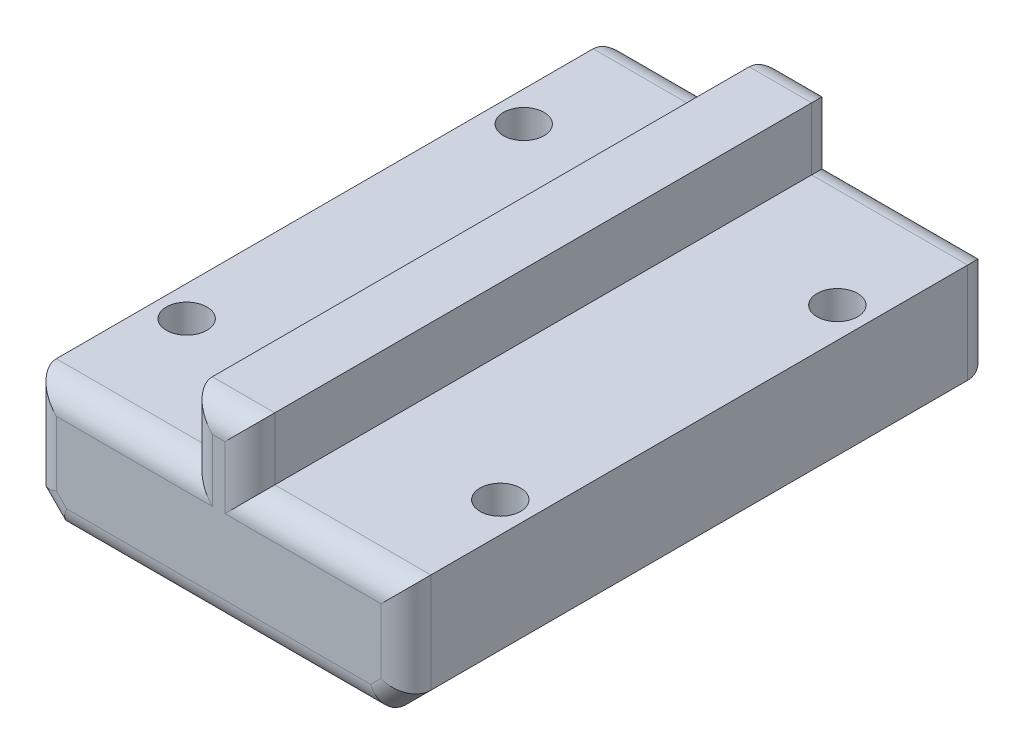
SolidWorks part; units mm, degrees
ref_plane "Front Plane" through (0, 0, 0) normal (0, 0, 1) x (1, 0, 0)
ref_plane "Top Plane" through (0, 0, 0) normal (0, 1, 0) x (1, 0, 0)
ref_plane "Right Plane" through (0, 0, 0) normal (1, 0, 0) x (0, 0, -1)
sketch "Sketch1" plane through (0, 0, 0) normal (0, 1, 0) x (1, 0, 0)
  line L1 (-15, -23.5) -> (15, -23.5)
  line L2 (-15, -23.5) -> (-15, 23.5)
  line L3 (-15, 23.5) -> (15, 23.5)
  line L4 (15, -23.5) -> (15, 23.5)
  line L5 (-15, -23.5) -> (15, 23.5) construction
  line L6 (-15, 23.5) -> (15, -23.5) construction
  point P0 (0, 0)
  dimension "D1" = 30
  dimension "D2" = 47
extrude "Boss-Extrude1" add sketch "Sketch1" along normal blind 10
sketch "Sketch2" plane through (0, 10, 0) normal (0, 1, 0) x (1, 0, 0)
  line L0 (15, 23.5) -> (-15, 23.5) construction
  line L1 (-2.5, -23.5) -> (2.5, -23.5)
  line L2 (-2.5, -23.5) -> (-2.5, 23.5)
  line L3 (-2.5, 23.5) -> (2.5, 23.5)
  line L4 (2.5, -23.5) -> (2.5, 23.5)
  line L5 (-2.5, -23.5) -> (2.5, 23.5) construction
  line L6 (-2.5, 23.5) -> (2.5, -23.5) construction
  point P0 (0, 0)
  dimension "D1" = 5
extrude "Boss-Extrude2" add sketch "Sketch2" along normal blind 5
sketch "Sketch3" plane through (0, 0, 0) normal (0, -1, 0) x (1, 0, 0)
  line L0 (-12.56, -23.5) -> (-12.56, -13.5) construction
  line L1 (15, -23.5) -> (-15, -23.5) construction
  line L2 (12.56, -23.5) -> (12.56, -13.5) construction
  line L3 (12.56, 23.5) -> (12.56, 13.5) construction
  line L4 (-15, 23.5) -> (15, 23.5) construction
  line L5 (-12.56, 23.5) -> (-12.56, 13.5) construction
  line L6 (-15, -23.5) -> (-15, 23.5) construction
  line L7 (15, 23.5) -> (15, -23.5) construction
  circle A0 centre (-12.56, 13.5) radius 1.625
  circle A1 centre (-12.56, -13.5) radius 1.625
  circle A2 centre (12.56, -13.5) radius 1.625
  circle A3 centre (12.56, 13.5) radius 1.625
  dimension "D7" = 3.25
  dimension "D8" = 3.25
  dimension "D9" = 3.25
  dimension "D10" = 3.25
  dimension "D1" = 10
  dimension "D2" = 2.44
  dimension "D3" = 2.44
  dimension "D4" = 10
  dimension "D5" = 10
  dimension "D6" = 10
extrude "Cut-Extrude1" cut sketch "Sketch3" against normal through all
sketch "Sketch4" plane through (0, 0, 0) normal (0, -1, 0) x (1, 0, 0)
  circle A0 centre (-12.56, 13.5) radius 2.7
  circle A1 centre (-12.56, -13.5) radius 2.7
  circle A2 centre (12.56, -13.5) radius 2.7
  circle A3 centre (12.56, 13.5) radius 2.7
  dimension "D1" = 5.4
  dimension "D2" = 5.4
  dimension "D3" = 5.4
  dimension "D4" = 5.4
extrude "Cut-Extrude2" cut sketch "Sketch4" against normal blind 1.45
chamfer "Chamfer1" distance 2 angle 45 1 edges at (-15, 0, 0)
chamfer "Chamfer2" distance 2 angle 45 1 edges at (15, 0, 0)
fillet "Fillet1" radius 2 10 edges at (-14, 1, 23.5) (-15, 6, 23.5) (0, 15, 23.5) (15, 6, 23.5) (14, 1, 23.5) (0, 0, 23.5)
fillet "Fillet2" radius 2 10 edges at (0, 15, -23.5) (-15, 6, -23.5) (-14, 1, -23.5) (0, 0, -23.5) (14, 1, -23.5) (15, 6, -23.5)
sketch "Mobious Logo" plane through (0, 0, 0) normal (0, -1, 0) x (1, 0, 0)
  line L0 (-8.9286, -5.3935) -> (-8.9286, -6.9382)
  line L1 (-8.9286, -6.9382) -> (0.654, -12.5149)
  line L2 (0.654, -12.5149) -> (0.654, -3.4298)
  line L3 (0.654, -3.4298) -> (-0.9494, -4.2487)
  line L4 (-0.9494, -4.2487) -> (-0.9494, -10.1586)
  line L5 (-0.9494, -10.1586) -> (-8.9286, -5.3935)
  line L6 (-4.0849, -5.6815) -> (-5.2369, -4.9745)
  line L7 (-5.2369, -4.9745) -> (2.6438, -0.4713)
  line L8 (2.6438, -0.4713) -> (2.6438, -12.1746)
  line L9 (2.6438, -12.1746) -> (1.0991, -12.5208)
  line L10 (1.0991, -12.5208) -> (1.0991, -2.5554)
  line L11 (1.0991, -2.5554) -> (-4.0849, -5.6815)
  line L12 (-1.4144, -9.3469) -> (-8.6929, -4.9745)
  line L13 (-8.6929, -4.9745) -> (0, 0)
  line L14 (0, 0) -> (-8.6929, 4.9484)
  line L15 (-8.6929, 4.9484) -> (-1.4144, 9.1135)
  line L16 (-1.4144, 9.1135) -> (-1.4144, 7.6251)
  line L17 (-1.4144, 7.6251) -> (-6.0919, 4.9484)
  line L18 (-6.0919, 4.9484) -> (2.4864, 0.0653)
  line L19 (2.4864, 0.0653) -> (-6.3206, -4.9745)
  line L20 (-6.3206, -4.9745) -> (-1.4144, -7.7674)
  line L21 (-1.4144, -7.7674) -> (-1.4144, -9.3469)
  line L22 (-8.9286, 5.3935) -> (-8.9286, 6.8596)
  line L23 (-8.9286, 6.8596) -> (0.654, 12.384)
  line L24 (0.654, 12.384) -> (0.654, 3.2727)
  line L25 (0.654, 3.2727) -> (-0.9494, 4.2938)
  line L26 (-0.9494, 4.2938) -> (-0.9494, 9.9753)
  line L27 (-0.9494, 9.9753) -> (-8.9286, 5.3935)
  line L28 (-5.2369, 4.9484) -> (2.6438, 0.4189)
  line L29 (2.6438, 0.4189) -> (2.6438, 11.9651)
  line L30 (2.6438, 11.9651) -> (1.0991, 12.5777)
  line L31 (1.0991, 12.5777) -> (1.0991, 2.4873)
  line L32 (1.0991, 2.4873) -> (-4.1438, 5.5006)
  line L33 (-4.1438, 5.5006) -> (-5.2369, 4.9484)
  line L34 (0, -21.5) -> (0, 21.5) construction
  line L35 (-13, -21.5) -> (13, -21.5) construction
  line L36 (13, 21.5) -> (-13, 21.5) construction
extrude "Cut-Extrude6" cut sketch "Mobious Logo" against normal blind 1.5 draft 4 draft outward yes
